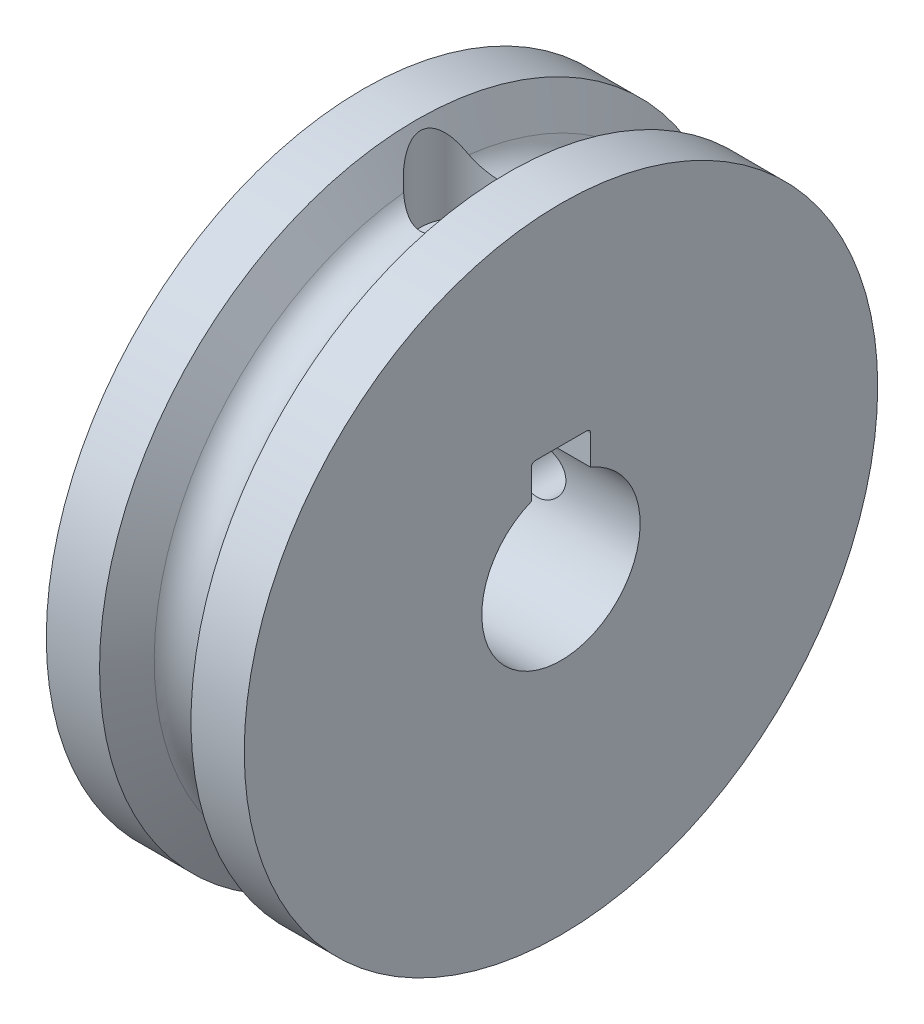
SolidWorks part; units mm, degrees
material "相當於S45C"
ref_plane "Front Plane" through (0, 0, 0) normal (0, 0, 1) x (1, 0, 0)
ref_plane "Top Plane" through (0, 0, 0) normal (0, 1, 0) x (1, 0, 0)
ref_plane "Right Plane" through (0, 0, 0) normal (1, 0, 0) x (0, 0, -1)
sketch "Sketch1" plane through (0, 0, 0) normal (0, 0, 1) x (1, 0, 0)
  line L0 (0, 4) -> (0, 16)
  line L5 (0, 16) -> (10, 16)
  line L6 (10, 16) -> (10, 4)
  line L7 (0, 0) -> (10, 0) construction
  line L8 (10, 4) -> (0, 4)
  line L9 (5, 16) -> (5, 0) construction
  dimension "T" = 10
  dimension "N" = 8
  dimension "D1." = 32
revolve "Revolve1" add sketch "Sketch1" angle 360 about L7
ref_plane "Plane1" through (0, 15, 0) normal (0, 1, 0) x (1, 0, 0)
sketch "Sketch2" plane through (0, 0, 0) normal (0, 0, 1) x (1, 0, 0)
  line L0 (5, 0) -> (5, 16) construction
  line L1 (10, -16) -> (10, 16) construction
  line L2 (0, 0) -> (10, 0) construction
  line L5 (0, 16) -> (0, -16) construction
  line L6 (5, 16) -> (7.1, 16)
  line L7 (5, 16) -> (5, 11.4)
  line L8 (5, 11.4) -> (7.1, 11.4)
  line L9 (7.1, 16) -> (7.1, 11.4)
  line L10 (0, 16) -> (10, 16) construction
  dimension "MSM_1" = 4.2
  dimension "D1" = 11.4
revolve "Cut-Revolve1" cut sketch "Sketch2" angle 360 about L9
hole_wizard "Tapped Hole1" positions "Sketch4" profile "Sketch3" tap size "M3x0.5" standard "JIS" end condition up to next
sketch "Sketch4" plane through (0, 15, 0) normal (0, 1, 0) x (1, 0, 0)
  line L0 (0, 0) -> (10, 0) construction
  line L1 (0, 16) -> (0, -16) construction
  line L3 (10, -16) -> (10, 16) construction
  point P0 (5, 0)
sketch "Sketch3" plane through (5, 15, 0) normal (1, 0, 0) x (0, 0, 1)
  line L0 (0, 0) -> (0, 31)
  line L1 (0, 31) -> (1.25, 31)
  line L2 (1.25, 31) -> (1.25, 0)
  line L5 (1.25, 0) -> (0, 0)
  line L11 (0, 0) -> (0, 31) construction
  dimension "Thru Tap Drill Dia." = 2.5
  dimension "Thru Tap Drill Depth" = 31
cosmetic thread "Hole Thread1" parameters "D1"=3
pattern_circular "CirPattern1" count 2 every 90 about axis through (0, 0, 0) along (-1, 0, 0) of "Cut-Revolve1", "Tapped Hole1"
pattern_circular "CirPattern2" [suppressed] count 2 every 90 of bodies 119
sketch "Sketch5" plane through (0, 0, 0) normal (1, 0, 0) x (0, 0, -1)
  line L0 (0, 0) -> (0, 4) construction
  line L1 (-1.5, 0) -> (1.5, 0)
  line L2 (-1.5, 0) -> (-1.5, 5.2)
  line L3 (-1.3, 5.4) -> (1.3, 5.4)
  line L4 (1.5, 0) -> (1.5, 5.2)
  arc A1 (1.3, 5.4) -> (1.5, 5.2) centre (1.3, 5.2) cw
  arc A2 (-1.5, 5.2) -> (-1.3, 5.4) centre (-1.3, 5.2) cw
  circle A3 centre (0, 0) radius 4 construction
  dimension "D1" = 0.2
  dimension "B_s" = 3
  dimension "T_s" = 1.4
extrude "Cut-Extrude1" cut sketch "Sketch5" along normal through all
sketch "Sketch6" [suppressed] plane through (0, 0, 0) normal (0, 0, 1) x (1, 0, 0)
  line L0 (0, 0) -> (10, 0) construction
  line L1 (10, -23.5) -> (10, 23.5) construction
  line L2 (5, 0) -> (5, 23.5) construction
  line L4 (2.9358, 23.5) -> (3.9713, 21)
  line L5 (3.9713, 21) -> (6.0287, 21)
  line L6 (6.0287, 21) -> (7.0642, 23.5)
  line L7 (7.0642, 23.5) -> (2.9358, 23.5)
  line L8 (3.35, 22.5) -> (6.65, 22.5) construction
  line L11 (0, 23.5) -> (10, 23.5) construction
  dimension "D1" = 45
  dimension "W" = 3.3
  dimension "D2." = 27
  dimension "D3" = 1
  dimension "H_s" = 1.5
  dimension "P.D." = 30
revolve "Cut-Revolve2" [suppressed] cut sketch "Sketch6" angle 360 about L0
sketch "Sketch7" plane through (0, 0, 0) normal (0, 0, 1) x (1, 0, 0)
  line L0 (0, 0) -> (10, 0) construction
  line L1 (10, -16) -> (10, 16) construction
  line L2 (5, 0) -> (5, 16) construction
  line L3 (0, 16) -> (10, 16) construction
  line L4 (2.6906, 16) -> (3.701, 14.25)
  line L5 (7.3094, 16) -> (6.299, 14.25)
  line L6 (2.6906, 16) -> (7.3094, 16)
  line L7 (0, 15) -> (10, 15) construction
  line L8 (10, 16) -> (10, 4) construction
  line L9 (0, 4) -> (0, 16) construction
  arc A0 (3.701, 14.25) -> (6.299, 14.25) centre (5, 15) ccw
  point P10 (5, 13.5)
  dimension "D1" = 60
  dimension "R" = 1.5
  dimension "D2." = 27
  dimension "H_s" = 1.5
  dimension "P.D." = 30
revolve "Cut-Revolve3" cut sketch "Sketch7" angle 360 about L7
sketch "Sketch8" [suppressed] plane through (0, 0, 0) normal (0, 0, 1) x (1, 0, 0)
  line L0 (0, 0) -> (10, 0) construction
  line L1 (10, -23.5) -> (10, 23.5) construction
  line L2 (0, 5) -> (0, 23.5) construction
  line L3 (0, 23.5) -> (10, 23.5) construction
  line L4 (0, 22.5) -> (10, 22.5) construction
  line L7 (0, 23.5) -> (10, 23.5)
  line L8 (0, 23.5) -> (0, 23.1)
  line L9 (0, 23.1) -> (10, 23.1)
  line L10 (10, 23.5) -> (10, 23.1)
  dimension "DC" = 46.2
  dimension "MSM_1" = 0.6
  dimension "P.D." = 30
revolve "Cut-Revolve4" [suppressed] cut sketch "Sketch8" angle 360 about L0
equation "\"D1@Sketch2\" = ( \"N@Sketch1\" / 2 ) + \"T_s@Sketch5\" + 6"
equation "\"Plane dim\"= \"P.D.\" * 0.5"
equation "\"Belt Radius\"= 1.5"
equation "\"Cut-Revolve1\"= if ( ( \"D1.@Sketch1\" - \"N@Sketch1\" ) / 2 - \"T_s@Sketch5\" > = 6 , \"unsuppressed\" , \"suppressed\" )"
equation "\"CirPattern1\" = if ( ( \"D1.@Sketch1\" - \"N@Sketch1\" ) / 2 - \"T_s@Sketch5\" > = 6 , \"unsuppressed\" , \"suppressed\" )"
equation "\"CirPattern2\" = if ( ( \"D1.@Sketch1\" - \"N@Sketch1\" ) / 2 - \"T_s@Sketch5\" > 6 , \"suppressed\" , \"unsuppressed\" )"
